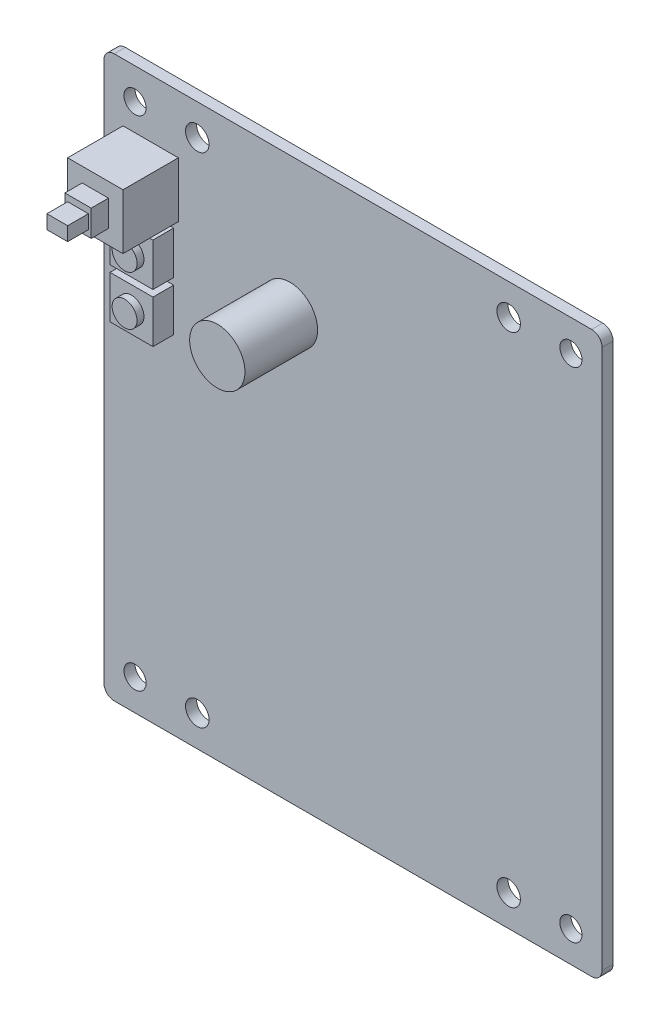
SolidWorks part; units mm, degrees
ref_plane "Alzado" through (0, 0, 0) normal (0, 0, 1) x (1, 0, 0)
ref_plane "Planta" through (0, 0, 0) normal (0, 1, 0) x (1, 0, 0)
ref_plane "Vista lateral" through (0, 0, 0) normal (1, 0, 0) x (0, 0, -1)
sketch "Model" plane through (0, 0, 0) normal (0, 0, 1) x (1, 0, 0)
  line L0 (79.0698, 220.6038) -> (79.0698, 298.6084)
  line L1 (7.0674, 298.6084) -> (7.0674, 220.6038)
  line L2 (8.5674, 219.1038) -> (77.5698, 219.1038)
  line L3 (77.5698, 300.1084) -> (8.5674, 300.1084)
  line L4 (76.4432, 280.3563) -> (73.4432, 280.3563)
  line L5 (76.4432, 232.4763) -> (76.4432, 280.3563)
  line L6 (73.4432, 232.4763) -> (76.4432, 232.4763)
  line L7 (73.4432, 280.3563) -> (73.4432, 232.4763)
  line L8 (28.1808, 232.4801) -> (28.1808, 271.1578)
  line L9 (25.1808, 232.4801) -> (28.1808, 232.4801)
  line L10 (25.1808, 271.1578) -> (25.1808, 232.4801)
  line L11 (9.2551, 269.0104) -> (9.2563, 226.8832)
  line L12 (18.685, 269.0104) -> (18.6863, 226.8832)
  line L13 (18.685, 269.0104) -> (9.2551, 269.0104)
  line L14 (18.6863, 226.8832) -> (9.2563, 226.8832)
  line L15 (37.929, 268.6584) -> (37.9301, 275.5694)
  line L16 (41.2725, 268.3584) -> (38.2289, 268.3584)
  line L17 (41.5725, 277.3009) -> (41.5725, 268.6584)
  line L18 (38.6121, 277.6009) -> (41.2725, 277.6009)
  line L19 (47.8995, 221.0056) -> (62.2048, 221.0056)
  line L20 (62.2048, 228.2055) -> (47.8995, 228.2055)
  line L21 (47.8995, 228.2055) -> (47.8995, 221.0056)
  line L22 (62.2048, 221.0056) -> (62.2048, 228.2055)
  line L23 (28.1941, 221.0056) -> (42.2994, 221.0056)
  line L24 (42.2994, 228.2055) -> (28.1941, 228.2055)
  line L25 (28.1941, 228.2055) -> (28.1941, 221.0056)
  line L26 (42.2994, 221.0056) -> (42.2994, 228.2055)
  line L27 (16.6077, 273.8998) -> (11.5077, 273.8998)
  line L28 (16.6077, 270.7998) -> (16.6077, 273.8998)
  line L29 (11.5077, 270.7998) -> (16.6077, 270.7998)
  line L30 (11.5077, 273.8998) -> (11.5077, 270.7998)
  line L31 (16.6077, 281.0451) -> (11.5077, 281.0451)
  line L32 (16.6077, 277.9451) -> (16.6077, 281.0451)
  line L33 (11.5077, 277.9451) -> (16.6077, 277.9451)
  line L34 (11.5077, 281.0451) -> (11.5077, 277.9451)
  line L35 (25.1808, 271.1578) -> (28.1808, 271.1578)
  line L36 (45.2171, 262.1628) -> (45.7171, 261.6628)
  line L37 (57.5171, 261.6628) -> (58.0171, 262.1628)
  line L38 (45.2171, 269.1628) -> (46.7171, 270.6628)
  line L39 (48.226, 270.6628) -> (46.7171, 270.6628)
  line L40 (45.2171, 269.1628) -> (45.2171, 262.1628)
  line L41 (58.0171, 262.1628) -> (58.0171, 269.1628)
  line L42 (45.7171, 261.6628) -> (57.5171, 261.6628)
  line L43 (57.8731, 273.6225) -> (48.826, 273.6225)
  line L44 (57.1392, 270.0406) -> (57.1392, 272.0907)
  line L45 (48.526, 270.9628) -> (48.526, 273.3225)
  line L46 (48.526, 270.9628) -> (48.226, 270.6628)
  line L47 (48.826, 273.6225) -> (48.526, 273.3225)
  line L48 (58.0171, 269.1628) -> (57.1392, 270.0406)
  line L49 (57.1392, 270.9628) -> (57.1392, 272.5218)
  line L50 (58.1732, 273.9225) -> (58.1739, 278.6843)
  line L51 (61.5165, 272.8218) -> (57.4392, 272.8218)
  line L52 (61.8165, 278.6843) -> (61.8165, 273.1218)
  line L53 (58.774, 278.9843) -> (61.5165, 278.9843)
  line L54 (71.3319, 235.3872) -> (64.3319, 235.3872)
  line L55 (71.3319, 248.1872) -> (71.8319, 247.6872)
  line L56 (71.8319, 235.8872) -> (71.3319, 235.3872)
  line L57 (64.3319, 248.1872) -> (62.8319, 246.6872)
  line L58 (62.8319, 245.1782) -> (62.8319, 246.6872)
  line L59 (64.3319, 248.1872) -> (71.3319, 248.1872)
  line L60 (71.8319, 247.6872) -> (71.8319, 235.8872)
  line L61 (59.8723, 236.5651) -> (59.8723, 244.5782)
  line L62 (63.4541, 236.2651) -> (61.4041, 236.2651)
  line L63 (62.5319, 244.8782) -> (60.1723, 244.8782)
  line L64 (62.5319, 244.8782) -> (62.8319, 245.1782)
  line L65 (59.8723, 244.5782) -> (60.1723, 244.8782)
  line L66 (64.3319, 235.3872) -> (63.4541, 236.2651)
  line L67 (62.5319, 236.2651) -> (60.1723, 236.2651)
  line L68 (59.8723, 236.5651) -> (60.1723, 236.2651)
  line L69 (41.5725, 277.3009) -> (41.2725, 277.6009)
  line L70 (41.5725, 268.6584) -> (41.2725, 268.3584)
  line L71 (38.2289, 268.3584) -> (37.929, 268.6584)
  line L72 (58.1739, 278.6843) -> (58.2618, 278.7722)
  line L73 (58.2618, 278.7722) -> (58.774, 278.9843)
  line L74 (61.5165, 278.9843) -> (61.8165, 278.6843)
  line L75 (61.5165, 272.8218) -> (61.8165, 273.1218)
  line L76 (33.9621, 275.8694) -> (37.6301, 275.8694)
  line L77 (38.3121, 280.2194) -> (38.3121, 277.9009)
  line L78 (38.3121, 277.9009) -> (38.6121, 277.6009)
  line L79 (37.6301, 275.8694) -> (37.9301, 275.5694)
  line L80 (57.8731, 273.6225) -> (58.1732, 273.9225)
  line L81 (57.4392, 272.8218) -> (57.1392, 272.5218)
  arc A0 (8.5674, 300.1084) -> (7.0674, 298.6084) centre (8.5674, 298.6084) ccw
  arc A1 (7.0674, 220.6038) -> (8.5674, 219.1038) centre (8.5674, 220.6038) ccw
  arc A2 (77.5698, 219.1038) -> (79.0698, 220.6038) centre (77.5698, 220.6038) ccw
  arc A3 (79.0698, 298.6084) -> (77.5698, 300.1084) centre (77.5698, 298.6084) ccw
  circle A4 centre (68.3041, 284.2311) radius 1
  circle A5 centre (13.8303, 287.7239) radius 3.7
  circle A6 centre (20.5667, 223.6035) radius 1.7
  circle A7 centre (65.5701, 223.6035) radius 1.7
  circle A8 centre (11.5671, 223.6035) radius 1.6003
  circle A9 centre (74.5698, 223.6035) radius 1.6003
  circle A10 centre (20.5667, 295.6084) radius 1.7
  circle A11 centre (65.5701, 295.6084) radius 1.7
  circle A12 centre (74.5698, 295.6084) radius 1.6003
  circle A13 centre (11.5671, 295.6084) radius 1.6003
  arc A14 (38.3121, 280.2194) -> (33.9621, 275.8694) centre (33.9621, 280.2194) ccw
extrude "Saliente-Extruir1" add sketch "Model" along normal blind 1.6 contours L14 L12 L13 L11 | L35 L10 L9 L8 | L27 L30 L29 L28 | L31 L34 L33 L32 | A5 | L77 A14 L76 L79 L15 L71 L16 L70 L17 L69 L18 L78 | L81 L51 L75 L52 L74 L53 L73 L72 L50 L80 L43 L47 L45 L46 L39 L38 L40 L36 L42 L37 L41 L48 L44 L49 | L61 L68 L67 L62 L66 L54 L56 L60 L55 L59 L57 L58 L64 L63 L65 | L4 L7 L6 L5 | L19 L22 L20 L21 | L23 L26 L24 L25 | L0 A3 L3 A0 L1 A1 L2 A2 A14 L77 L78 L18 L69 L17 L70 L16 L71 L15 L79 L76 A13 A12 A11 A10 A9 A8 A7 A6 A5 A4 L51 L81 L49 L44 L48 L41 L37 L42 | A4 region at (44.5131, 262.02, 0) region at (74.9432, 256.4163, 0) region at (26.6808, 251.819, 0) region at (13.9707, 247.9468, 0) region at (36.0911, 277.5833, 0) region at (55.0521, 224.6056, 0) region at (35.2468, 224.6056, 0) region at (14.0577, 272.3498, 0) region at (14.0577, 279.4951, 0) region at (53.0046, 268.4435, 0) region at (66.2845, 241.5576, 0) region at (68.3041, 284.2311, 0) region at (13.8303, 287.7239, 0)
sketch "Croquis2" plane through (0, 0, 1.6) normal (0, 0, 1) x (1, 0, 0)
  line L0 (7.0674, 298.6084) -> (7.0674, 300.1084) construction
  line L1 (7.0674, 300.1084) -> (13.8303, 300.1084) construction
  line L2 (77.5698, 300.1084) -> (8.5674, 300.1084) construction
  line L3 (13.8303, 300.1084) -> (13.8303, 287.7239) construction
  line L4 (7.0674, 219.1038) -> (9.2563, 219.1038) construction
  line L5 (8.5674, 219.1038) -> (77.5698, 219.1038) construction
  line L6 (9.2563, 219.1038) -> (18.6863, 219.1038) construction
  line L7 (18.6863, 219.1038) -> (18.6863, 226.8832) construction
  line L8 (18.6863, 226.8832) -> (18.6863, 269.0104) construction
  line L9 (18.6863, 269.0104) -> (9.2563, 269.0104) construction
  line L10 (9.2563, 269.0104) -> (9.2563, 226.8832) construction
  line L11 (9.2563, 226.8832) -> (18.6863, 226.8832) construction
  line L12 (7.0674, 300.1084) -> (7.0674, 281.0451) construction
  line L13 (7.0674, 298.6084) -> (7.0674, 220.6038) construction
  line L14 (7.0674, 281.0451) -> (7.0674, 277.9451) construction
  line L15 (7.0674, 277.9451) -> (7.0674, 273.8998) construction
  line L16 (7.0674, 273.8998) -> (7.0674, 270.7998) construction
  line L17 (7.0674, 270.7998) -> (11.5077, 270.7998) construction
  line L18 (11.5077, 270.7998) -> (16.6077, 270.7998) construction
  line L19 (16.6077, 270.7998) -> (16.6077, 273.8998) construction
  line L20 (16.6077, 273.8998) -> (11.5077, 273.8998) construction
  line L21 (11.5077, 273.8998) -> (11.5077, 270.7998) construction
  line L22 (11.5077, 277.9451) -> (11.5077, 281.0451) construction
  line L23 (11.5077, 281.0451) -> (16.6077, 281.0451) construction
  line L24 (16.6077, 281.0451) -> (16.6077, 277.9451) construction
  line L25 (16.6077, 277.9451) -> (11.5077, 277.9451) construction
  line L26 (79.0698, 219.1038) -> (79.0698, 221.0056) construction
  line L27 (79.0698, 220.6038) -> (79.0698, 298.6084) construction
  line L28 (79.0698, 221.0056) -> (79.0698, 228.2055) construction
  line L29 (79.0698, 221.0056) -> (62.2048, 221.0056) construction
  line L30 (62.2048, 221.0056) -> (47.8995, 221.0056) construction
  line L31 (47.8995, 221.0056) -> (42.2994, 221.0056) construction
  line L32 (42.2994, 221.0056) -> (28.1941, 221.0056) construction
  line L33 (28.1941, 221.0056) -> (28.1941, 228.2055) construction
  line L34 (28.1941, 228.2055) -> (42.2994, 228.2055) construction
  line L35 (42.2994, 228.2055) -> (42.2994, 221.0056) construction
  line L36 (47.8995, 221.0056) -> (47.8995, 228.2055) construction
  line L37 (62.2048, 228.2055) -> (62.2048, 221.0056) construction
  line L38 (47.8995, 228.2055) -> (62.2048, 228.2055) construction
  line L39 (79.0698, 219.1038) -> (79.0698, 232.4763) construction
  line L40 (79.0698, 232.4763) -> (79.0698, 280.3563) construction
  line L41 (79.0698, 280.3563) -> (76.4432, 280.3563) construction
  line L42 (76.4432, 280.3563) -> (73.4432, 280.3563) construction
  line L43 (76.4432, 280.3563) -> (76.4432, 232.4763) construction
  line L44 (76.4432, 232.4763) -> (73.4432, 232.4763) construction
  line L45 (73.4432, 232.4763) -> (73.4432, 280.3563) construction
  line L46 (73.4432, 232.4763) -> (28.1808, 232.4763) construction
  line L47 (28.1808, 232.4763) -> (25.1808, 232.4763) construction
  line L48 (28.1808, 232.4763) -> (28.1808, 271.1539) construction
  line L49 (28.1808, 271.1539) -> (25.1808, 271.1539) construction
  line L50 (25.1808, 271.1539) -> (25.1808, 232.4763) construction
  line L51 (37.6301, 300.1084) -> (41.2725, 300.1084) construction
  line L52 (41.2725, 300.1084) -> (41.5725, 300.1084) construction
  line L53 (41.5725, 300.1084) -> (41.5725, 277.3009) construction
  line L54 (41.5725, 277.3009) -> (41.5725, 268.6584) construction
  line L55 (41.5725, 268.6584) -> (41.5725, 268.3584) construction
  line L56 (41.5725, 268.3584) -> (41.2725, 268.3584)
  line L57 (41.2725, 268.3584) -> (38.2289, 268.3584)
  line L58 (38.2289, 268.3584) -> (37.9289, 268.3584) construction
  line L59 (37.9289, 268.3584) -> (37.9289, 268.6584) construction
  line L60 (37.9289, 268.6584) -> (37.9289, 275.5694) construction
  line L61 (37.9289, 275.5694) -> (37.9289, 275.8694) construction
  line L62 (37.9289, 275.8694) -> (37.6289, 275.8694) construction
  circle A0 centre (13.8303, 287.7239) radius 3.7
  dimension "D3" = 7.4
  dimension "D14" = 1.9018
  dimension "D26" = 30.5627
  dimension "D32" = 0.3
  dimension "D1" = 6.7629
  dimension "D2" = 12.3846
  dimension "D4" = 2.1889
  dimension "D5" = 9.43
  dimension "D6" = 7.7794
  dimension "D7" = 42.1272
  dimension "D8" = 19.0633
  dimension "D9" = 3.1
  dimension "D10" = 3.1
  dimension "D11" = 4.0454
  dimension "D12" = 4.4403
  dimension "D13" = 5.1
  dimension "D15" = 7.1999
  dimension "D16" = 16.865
  dimension "D17" = 14.3053
  dimension "D18" = 5.6001
  dimension "D19" = 14.1053
  dimension "D20" = 13.3724
  dimension "D21" = 2.6266
  dimension "D22" = 3
  dimension "D23" = 45.2624
  dimension "D24" = 3
  dimension "D25" = 38.6776
  dimension "D27" = 3.6423
  dimension "D28" = 0.3
  dimension "D29" = 0.3
  dimension "D30" = 22.8076
  dimension "D31" = 8.6425
  dimension "D33" = 0.3
  dimension "D34" = 3.0436
  dimension "D35" = 0.3
  dimension "D36" = 6.911
  dimension "D37" = 0.3
  dimension "D38" = 0.3
sketch "Croquis3" plane through (0, 0, 1.6) normal (0, 0, 1) x (1, 0, 0)
  line L1 (9.8303, 291.7239) -> (17.8303, 291.7239)
  line L2 (9.8303, 291.7239) -> (9.8303, 283.7239)
  line L3 (13.9713, 269.0104) -> (13.9713, 261.9904) construction
  line L4 (18.6863, 269.0104) -> (9.2563, 269.0104) construction
  line L5 (13.9713, 261.9904) -> (13.9713, 254.9704) construction
  line L6 (13.9713, 254.9704) -> (13.9713, 247.9504) construction
  line L7 (13.9713, 247.9504) -> (13.9713, 240.9304) construction
  line L8 (13.9713, 240.9304) -> (13.9713, 233.9104) construction
  line L9 (13.9713, 233.9104) -> (13.9713, 226.8832) construction
  line L10 (13.9713, 261.9904) -> (18.6863, 261.9904) construction
  line L11 (9.8303, 283.7239) -> (17.8303, 283.7239)
  line L12 (18.6863, 226.8832) -> (18.6863, 269.0104) construction
  line L13 (13.9713, 254.9704) -> (18.6863, 254.9704) construction
  line L14 (18.6863, 254.9704) -> (18.6066, 255.0123) construction
  line L15 (13.9713, 247.9504) -> (18.6863, 247.9468) construction
  line L16 (13.9713, 240.9304) -> (18.6863, 240.9304) construction
  line L17 (13.9713, 233.9104) -> (18.6863, 233.9104) construction
  line L18 (18.6863, 233.9104) -> (18.6782, 234.0129) construction
  line L19 (9.2563, 226.8832) -> (18.6863, 226.8832) construction
  line L20 (17.8303, 291.7239) -> (17.8303, 283.7239)
  line L21 (28.1941, 224.6056) -> (35.2491, 224.6056) construction
  line L22 (28.1941, 221.0056) -> (28.1941, 228.2055) construction
  line L23 (35.2491, 224.6056) -> (42.2994, 224.6056) construction
  line L24 (42.2994, 228.2055) -> (42.2994, 221.0056) construction
  line L25 (35.2491, 224.6056) -> (35.2468, 228.2055) construction
  line L26 (28.1941, 228.2055) -> (42.2994, 228.2055) construction
  line L27 (9.8303, 291.7239) -> (17.8303, 283.7239) construction
  line L28 (9.8303, 283.7239) -> (17.8303, 291.7239) construction
  point P0 (13.8303, 287.7239)
  dimension "D1" = 7.02
  dimension "D7" = 7.0503
  dimension "D2" = 7.02
  dimension "D3" = 7.02
  dimension "D4" = 7.02
  dimension "D5" = 7.02
  dimension "D6" = 7.055
  dimension "D8" = 8
  dimension "D9" = 8
extrude "Saliente-Extruir2" add sketch "Croquis3" along normal blind 8
sketch "Croquis4" plane through (0, 0, 9.6) normal (0, 0, 1) x (1, 0, 0)
  line L1 (11.9303, 289.6239) -> (15.7303, 289.6239)
  line L2 (11.9303, 289.6239) -> (11.9303, 285.8239)
  line L3 (11.9303, 285.8239) -> (15.7303, 285.8239)
  line L4 (15.7303, 289.6239) -> (15.7303, 285.8239)
  line L5 (11.9303, 289.6239) -> (15.7303, 285.8239) construction
  line L6 (11.9303, 285.8239) -> (15.7303, 289.6239) construction
  point P0 (13.8303, 287.7239)
  dimension "D1" = 3.8
  dimension "D2" = 3.8
extrude "Saliente-Extruir3" add sketch "Croquis4" along normal blind 2.5
sketch "Croquis5" plane through (0, 0, 12.1) normal (0, 0, 1) x (1, 0, 0)
  line L1 (12.3303, 288.7239) -> (15.3303, 288.7239)
  line L2 (12.3303, 288.7239) -> (12.3303, 286.7239)
  line L3 (12.3303, 286.7239) -> (15.3303, 286.7239)
  line L4 (15.3303, 288.7239) -> (15.3303, 286.7239)
  line L5 (12.3303, 288.7239) -> (15.3303, 286.7239) construction
  line L6 (12.3303, 286.7239) -> (15.3303, 288.7239) construction
  point P0 (13.8303, 287.7239)
  dimension "D1" = 2
  dimension "D2" = 3
extrude "Saliente-Extruir4" add sketch "Croquis5" along normal blind 3
sketch "Croquis6" plane through (0, 0, 1.6) normal (0, 0, 1) x (1, 0, 0)
  line L0 (14.0577, 281.0451) -> (14.0577, 277.9451) construction
  line L1 (11.5077, 281.0451) -> (16.6077, 281.0451) construction
  line L2 (16.6077, 277.9451) -> (11.5077, 277.9451) construction
  line L3 (16.6077, 279.4951) -> (11.5077, 279.4951) construction
  line L4 (16.6077, 281.0451) -> (16.6077, 277.9451) construction
  line L5 (11.5077, 277.9451) -> (11.5077, 281.0451) construction
  line L6 (14.0577, 273.8998) -> (14.0577, 270.7998) construction
  line L7 (16.6077, 273.8998) -> (11.5077, 273.8998) construction
  line L8 (11.5077, 270.7998) -> (16.6077, 270.7998) construction
  line L9 (16.6077, 272.3498) -> (11.5077, 272.3498) construction
  line L10 (16.6077, 270.7998) -> (16.6077, 273.8998) construction
  line L11 (11.5077, 273.8998) -> (11.5077, 270.7998) construction
  line L13 (10.9577, 282.5951) -> (17.1577, 282.5951)
  line L14 (10.9577, 282.5951) -> (10.9577, 276.3951)
  line L15 (10.9577, 276.3951) -> (17.1577, 276.3951)
  line L16 (17.1577, 282.5951) -> (17.1577, 276.3951)
  line L17 (10.9577, 282.5951) -> (17.1577, 276.3951) construction
  line L18 (10.9577, 276.3951) -> (17.1577, 282.5951) construction
  line L19 (10.9577, 275.4498) -> (17.1577, 275.4498)
  line L20 (10.9577, 275.4498) -> (10.9577, 269.2498)
  line L21 (10.9577, 269.2498) -> (17.1577, 269.2498)
  line L22 (17.1577, 275.4498) -> (17.1577, 269.2498)
  line L23 (10.9577, 275.4498) -> (17.1577, 269.2498) construction
  line L24 (10.9577, 269.2498) -> (17.1577, 275.4498) construction
  point P24 (14.0577, 279.4951)
  point P29 (14.0577, 272.3498)
  dimension "D1" = 6.2
  dimension "D2" = 6.2
  dimension "D3" = 6.2
  dimension "D4" = 6.2
extrude "Saliente-Extruir5" add sketch "Croquis6" along normal blind 3
sketch "Croquis7" plane through (0, 0, 4.6) normal (0, 0, 1) x (1, 0, 0)
  line L0 (14.0577, 281.0451) -> (14.0577, 277.9451) construction
  line L1 (11.5077, 281.0451) -> (16.6077, 281.0451) construction
  line L2 (16.6077, 277.9451) -> (11.5077, 277.9451) construction
  line L3 (16.6077, 279.4951) -> (11.5077, 279.4951) construction
  line L4 (16.6077, 281.0451) -> (16.6077, 277.9451) construction
  line L5 (11.5077, 277.9451) -> (11.5077, 281.0451) construction
  line L6 (14.0577, 273.8998) -> (14.0577, 270.7998) construction
  line L7 (16.6077, 273.8998) -> (11.5077, 273.8998) construction
  line L8 (11.5077, 270.7998) -> (16.6077, 270.7998) construction
  line L9 (16.6077, 272.3498) -> (11.5077, 272.3498) construction
  line L10 (16.6077, 270.7998) -> (16.6077, 273.8998) construction
  line L11 (11.5077, 273.8998) -> (11.5077, 270.7998) construction
  line L12 (11.5077, 272.3498) -> (11.4754, 272.3826) construction
  circle A0 centre (14.0577, 279.4951) radius 1.8
  circle A1 centre (14.0577, 272.3498) radius 1.8
extrude "Saliente-Extruir6" add sketch "Croquis7" along normal blind 1
sketch "Croquis8" plane through (0, 0, 1.6) normal (0, 0, 1) x (1, 0, 0)
  line L0 (7.0674, 300.1084) -> (33.9621, 300.1084) construction
  line L1 (77.5698, 300.1084) -> (8.5674, 300.1084) construction
  line L2 (33.9621, 300.1084) -> (33.9621, 280.2194) construction
  circle A0 centre (33.9621, 280.2194) radius 4
  dimension "D3" = 8
  dimension "D1" = 26.8947
  dimension "D2" = 19.889
extrude "Saliente-Extruir7" add sketch "Croquis8" along normal blind 10.5
